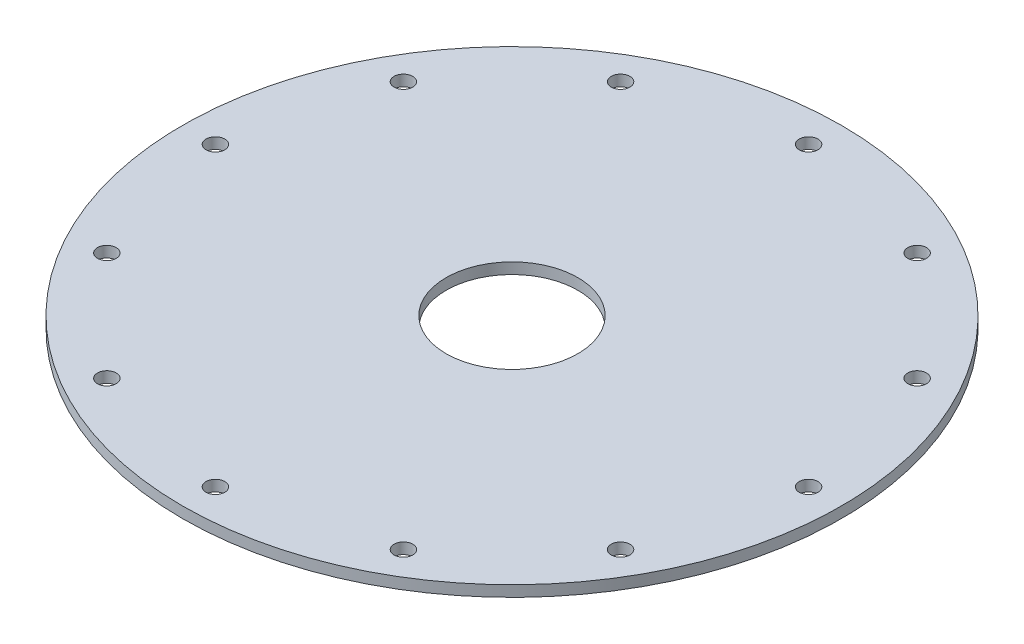
SolidWorks part; units mm, degrees
material "6063-T6"
ref_plane "Front Plane" through (0, 0, 0) normal (0, 0, 1) x (1, 0, 0)
ref_plane "Top Plane" through (0, 0, 0) normal (0, 1, 0) x (1, 0, 0)
ref_plane "Right Plane" through (0, 0, 0) normal (1, 0, 0) x (0, 0, -1)
ref_axis "Axis1" through (0, 55, 0) along (0, -1, 0)
sketch "Sketch1" plane through (0, 0, 0) normal (0, 0, 1) x (1, 0, 0)
  line L0 (-47.625, 0) -> (-9.525, 0)
  line L1 (0, 55) -> (0, -55) construction
  line L2 (-47.625, 0) -> (-47.625, 1.5875)
  line L3 (-47.625, 1.5875) -> (-9.525, 1.5875)
  line L4 (-47.625, 1.5875) -> (-9.525, 1.5875) construction
  line L5 (-9.525, 1.5875) -> (-9.525, 0)
  line L6 (-9.525, 0) -> (0, 0) construction
  line L7 (-47.625, 0) -> (-47.625, 1.5875) construction
  line L8 (-9.525, 1.5875) -> (-9.525, 0) construction
revolve "Revolve1" add sketch "Sketch1" angle 360 about axis through (0, 55, 0) along (0, -1, 0)
ref_plane "Hole Location Plane" through (0, 3.175, 0) normal (0, 1, 0) x (1, 0, 0)
sketch "Hole Location" plane through (0, 3.175, 0) normal (0, 1, 0) x (1, 0, 0)
  line L0 (0, 0) -> (-42.8625, 0) construction
  circle A0 centre (0, 0) radius 42.8625 construction
  dimension "D1" = 85.725
hole_wizard "#36 (0.1065) Diameter Hole1" positions "Sketch4" profile "Sketch5" hole size "#36" standard "ANSI Inch" end condition through all
sketch "Sketch4" plane through (0, 1.5875, 0) normal (0, 1, 0) x (1, 0, 0)
  point P0 (-42.8625, 0)
sketch "Sketch5" plane through (-42.8625, 1.5875, 0) normal (1, 0, 0) x (0, 0, 1)
  line L0 (0, 0) -> (0, 1.5875)
  line L1 (0, 1.5875) -> (1.3525, 1.5875)
  line L2 (1.3525, 1.5875) -> (1.3525, 0)
  line L5 (1.3525, 0) -> (0, 0)
  line L11 (0, -6.35) -> (0, 107.95) construction
  dimension "Thru Hole Dia." = 2.7051
  dimension "Thru Hole Depth" = 1.5875
pattern_circular "CirPattern1" count 12 every 30 about axis through (0, 55, 0) along (0, -1, 0) of "#36 (0.1065) Diameter Hole1"
equation "\"D1@Hole Location\"=\"TANK DIAMETER@Cryo Tank.Assembly\"+\"GASKET SEAT THICKNESS@Cryo Tank.Assembly\""
